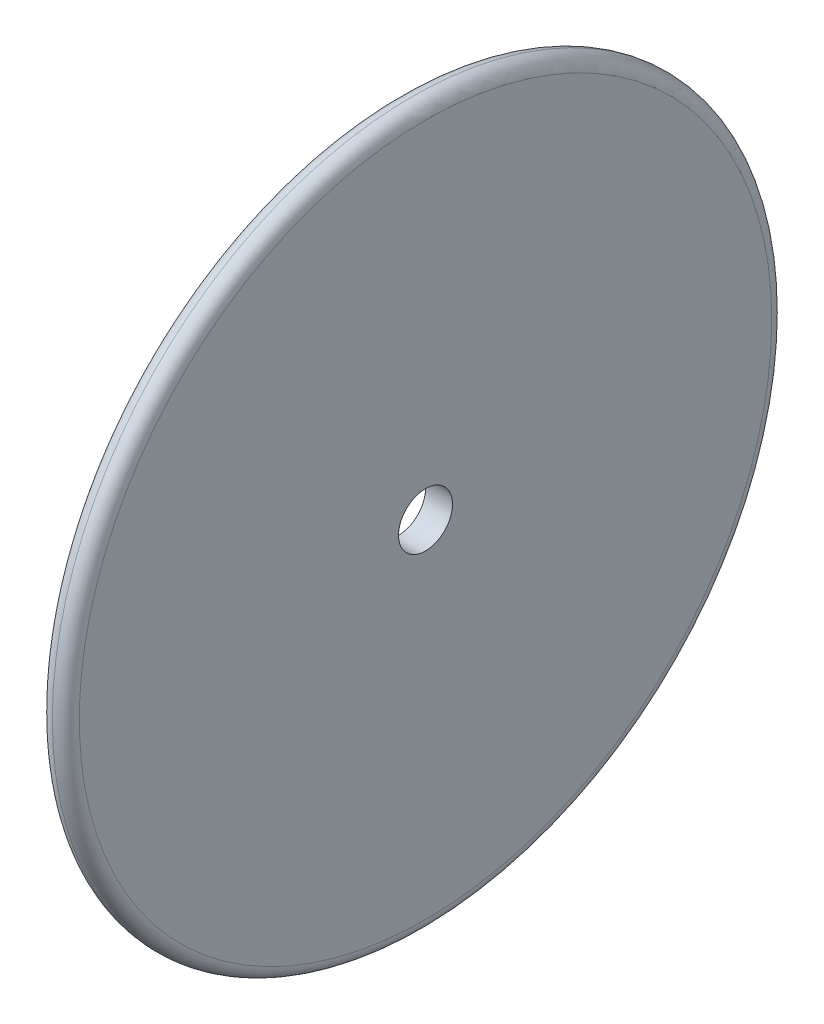
SolidWorks part; units mm, degrees
ref_plane "Front Plane" through (0, 0, 0) normal (1, 0, 0) x (0, 1, 0)
ref_plane "Top Plane" through (0, 0, 0) normal (0, 0, 1) x (0, 1, 0)
ref_plane "Right Plane" through (0, 0, 0) normal (0, 1, 0) x (-1, 0, 0)
sketch "Sketch1" plane through (0, 0, 0) normal (1, 0, 0) x (0, 1, 0)
  circle A0 centre (0, 0) radius 20
  circle A1 centre (0, 0) radius 1.5
  dimension "D1" = 40
  dimension "D2" = 3
extrude "Boss-Extrude2" add sketch "Sketch1" along normal blind 1.5
fillet "Fillet1" radius 0.75 2 edges at (1.5, 0, -20) (0, 0, -20)
